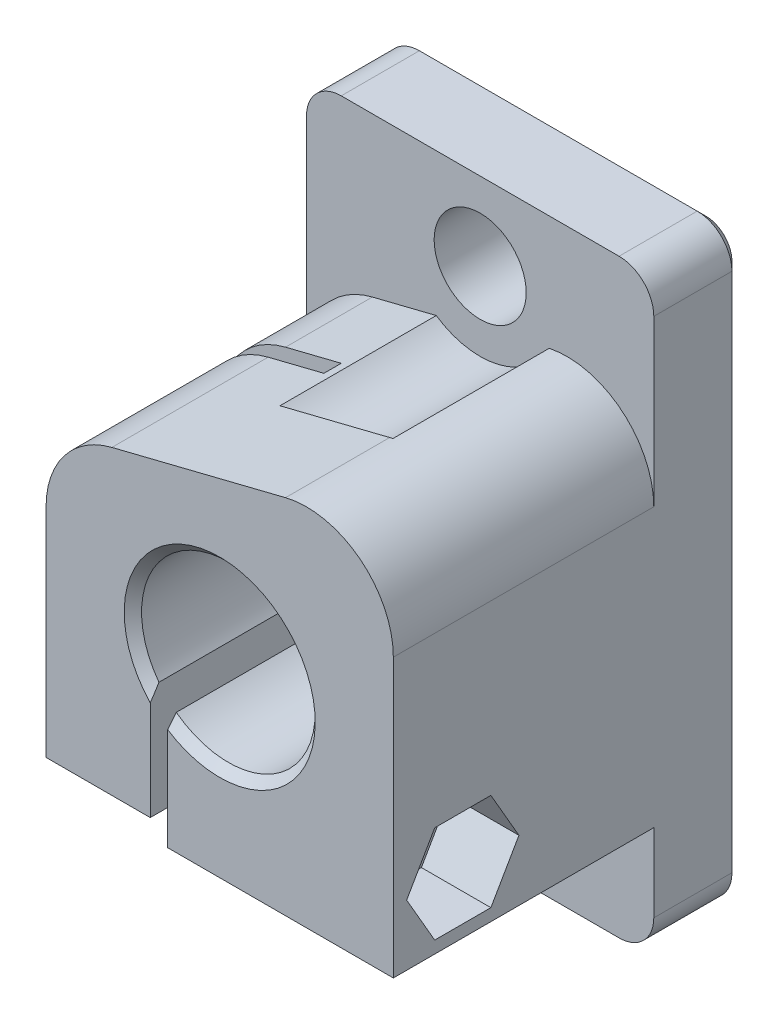
SolidWorks part; units mm, degrees
ref_plane "Plano frontal" through (0, 0, 0) normal (0, 0, 1) x (1, 0, 0)
ref_plane "Plano superior" through (0, 0, 0) normal (0, 1, 0) x (1, 0, 0)
ref_plane "Plano direito" through (0, 0, 0) normal (1, 0, 0) x (0, 0, -1)
sketch "Esboço1" plane through (0, 0, 0) normal (0, 0, 1) x (1, 0, 0)
  line L1 (0, 0) -> (20, 0)
  line L2 (0, 0) -> (0, 34)
  line L3 (0, 34) -> (20, 34)
  line L4 (20, 0) -> (20, 34)
  circle A0 centre (10, 17) radius 5
  circle A1 centre (10, 29.5) radius 2.65
  circle A2 centre (10, 4.5) radius 2.65
  point P14 (10, 34)
  dimension "D3" = 10
  dimension "D4" = 5.3
  dimension "D1" = 34
  dimension "D2" = 20
  dimension "D5" = 4.5
  dimension "D6" = 4.5
  dimension "D7" = 17
extrude "Ressalto-extrusão1" add sketch "Esboço1" along normal blind 5
sketch "Esboço2" plane through (0, 0, 0) normal (0, 0, -1) x (-1, 0, 0)
  line L0 (0, 23.9149) -> (-20, 28.9014)
  line L1 (0, 34) -> (0, 0) construction
  line L2 (-20, 0) -> (-20, 34) construction
  line L3 (0, 23.9149) -> (0, 6.5)
  line L4 (0, 6.5) -> (-20, 6.5)
  line L5 (-20, 28.9014) -> (-20, 6.5)
  circle A0 centre (-10, 17) radius 5 construction
  circle A1 centre (-10, 17) radius 5
  circle A2 centre (-10, 29.5) radius 2.65 construction
  circle A3 centre (-10, 4.5) radius 2.65 construction
  circle A4 centre (-10, 29.5) radius 4.5 construction
  dimension "D3" = 3
  dimension "D2" = 2
  dimension "D8" = 9
  dimension "D1" = 76
extrude "Ressalto-extrusão2" add sketch "Esboço2" against normal blind 20
sketch "Esboço3" plane through (0, 0, 20) normal (0, 0, 1) x (1, 0, 0)
  line L0 (6, 14) -> (6, 7.5)
  line L1 (6, 7.5) -> (0, 7.5)
  line L2 (0, 6.5) -> (0, 23.9149) construction
  line L3 (0, 7.5) -> (0, 6.5)
  line L4 (0, 6.5) -> (7, 6.5)
  line L5 (20, 6.5) -> (11.7385, 6.5) construction
  line L6 (7, 6.5) -> (7, 13)
  circle A0 centre (10, 17) radius 5 construction
  arc A1 (6, 14) -> (7, 13) centre (10, 17) ccw
  dimension "D1" = 1
  dimension "D2" = 1
  dimension "D3" = 6
extrude "Corte-extrusão1" cut sketch "Esboço3" against normal blind 9
sketch "Esboço5" plane through (0, 0, 0) normal (-1, 0, 0) x (0, 0, 1)
  line L1 (11, 6.5) -> (20, 6.5) construction
  line L2 (20, 7.5) -> (20, 23.9149) construction
  circle A0 centre (16, 10) radius 1.65
  dimension "D1" = 3.3
  dimension "D2" = 3.5
  dimension "D3" = 4
extrude "Corte-extrusão3" cut sketch "Esboço5" against normal up to surface (20 mm away) up to face at (20, 17.3504, 7.5)
sketch "Esboço4" plane through (20, 0, 0) normal (1, 0, 0) x (0, 0, -1)
  line L1 (-19.2332, 10) -> (-17.6166, 7.2)
  line L2 (-17.6166, 7.2) -> (-14.3834, 7.2)
  line L3 (-14.3834, 7.2) -> (-12.7668, 10)
  line L4 (-12.7668, 10) -> (-14.3834, 12.8)
  line L5 (-14.3834, 12.8) -> (-17.6166, 12.8)
  line L6 (-17.6166, 12.8) -> (-19.2332, 10)
  line L7 (0, 0) -> (0, 34) construction
  line L8 (-20, 12.8) -> (-17.6166, 12.8) construction
  line L9 (-20, 12.8) -> (-20, 7.2) construction
  line L10 (-20, 28.9014) -> (-20, 6.5) construction
  line L11 (-20, 7.2) -> (-17.6166, 7.2) construction
  circle A0 centre (-16, 10) radius 2.8 construction
  circle A1 centre (-16, 10) radius 1.65 construction
  circle A2 centre (-16, 10) radius 1.65 construction
  dimension "D1" = 5.6
extrude "Corte-extrusão2" cut sketch "Esboço4" against normal blind 4 from surface starting at face at (20, 10, 17.65)
fillet "Filete1" radius 5 2 edges at (0, 23.9149, 12.5) (20, 28.9014, 12.5)
fillet "Filete2" radius 2 4 edges at (20, 0, 2.5) (0, 0, 2.5) (20, 34, 2.5) (0, 34, 2.5)
sketch "Esboço6" plane through (0, 0, 20) normal (0, 0, 1) x (1, 0, 0)
  circle A0 centre (10, 4.5) radius 4.75
  dimension "D1" = 9.5
extrude "Corte-extrusão4" cut sketch "Esboço6" along normal blind 8 from surface starting at face at (10, 3.0652, 5)
sketch "Esboço7" plane through (0, 0, 0) normal (0, 0, -1) x (-1, 0, 0)
  circle A0 centre (-10, 17) radius 5 construction
  circle A1 centre (-10, 17) radius 5
extrude "Ressalto-extrusão3" add sketch "Esboço7" against normal blind 10
sketch "Esboço8" plane through (0, 0, 0) normal (-1, 0, 0) x (0, 0, 1)
  line L0 (20, 27.5017) -> (5, 27.5017) construction
  line L1 (11, 6.5) -> (10, 6.5)
  line L2 (11, 6.5) -> (11, 27.5017)
  line L3 (11, 27.5017) -> (10, 27.5017)
  line L4 (10, 6.5) -> (10, 27.5017)
  dimension "D1" = 1
extrude "Corte-extrusão5" cut sketch "Esboço8" against normal up to surface (7 mm away) up to face at (7, 11.65, 16)
sketch "Esboço10" plane through (0, 0, 5) normal (0, 0, 1) x (1, 0, 0)
  circle A0 centre (10, 29.5) radius 4.5
  dimension "D1" = 9
extrude "Corte-extrusão7" cut sketch "Esboço10" along normal blind 8
chamfer "Chanfro5" distance 1 angle 60 3 edges at (13.8839, 27.3756, 13) (10.6308, 26.5654, 13) (10.6542, 6.5, 13) first distance on face at (16.314, 26.2417, 12.6667) first distance on face at (7.1685, 25.7022, 11.8) first distance on face at (13.7695, 6.5, 12.6667)
sketch "Esboço11" plane through (0, 0, 5) normal (0, 0, 1) x (1, 0, 0)
  arc A0 (8.2615, 6.5) -> (11.7385, 6.5) centre (10, 4.5) ccw construction
  arc A1 (8.2615, 6.5) -> (11.7385, 6.5) centre (10, 4.5) ccw
  arc A2 (8.2615, 6.5) -> (11.7385, 6.5) centre (10, 4.5) cw
extrude "Corte-extrusão8" cut sketch "Esboço11" against normal blind 10
chamfer "Chanfro2" distance 0.5 angle 45 11 edges at (12.65, 4.5, 0) (12.65, 29.5, 0) (19.4142, 33.4142, 0) (10, 34, 0) (0.5858, 33.4142, 0) (0, 17, 0) (0.5858, 0.5858, 0) (10, 0, 0) (19.4142, 0.5858, 0) (13.5355, 20.5355, 20) (20, 17, 0)
